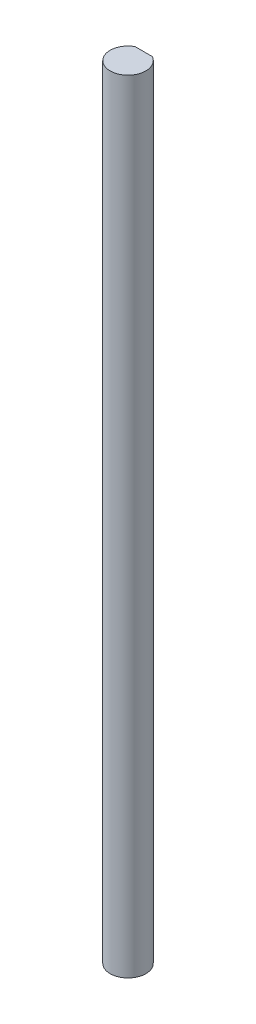
SolidWorks part; units mm, degrees
material "AISI 1045 Steel, cold drawn"
ref_plane "Front Plane" through (0, 0, 0) normal (0, 0, 1) x (1, 0, 0)
ref_plane "Top Plane" through (0, 0, 0) normal (0, 1, 0) x (1, 0, 0)
ref_plane "Right Plane" through (0, 0, 0) normal (1, 0, 0) x (0, 0, -1)
sketch "Sketch1" plane through (0, 0, 0) normal (0, 1, 0) x (1, 0, 0)
  line L0 (-1.9365, 3.5) -> (1.9365, 3.5)
  arc A0 (-1.9365, 3.5) -> (1.9365, 3.5) centre (0, 0) ccw
  dimension "D1" = 8
  dimension "D2" = 3.5
extrude "Boss-Extrude1" add sketch "Sketch1" along normal blind 175
hole_wizard "Tap Drill for M3x0.5 Tap1" positions "Sketch2" profile "Sketch3" hole size "M3x0.5" standard "ANSI Metric"
sketch "Sketch2" plane through (0, 0, -3.5) normal (0, 0, -1) x (-1, 0, 0)
  line L0 (-1.9365, 175) -> (1.9365, 175) construction
  point P0 (0, 171.5)
  point P5 (0, 175)
  dimension "D1" = 3.5
sketch "Sketch3" plane through (0, 171.5, -3.5) normal (1, 0, 0) x (0, 1, 0)
  line L0 (0, 0) -> (0, 5.7511)
  line L1 (0, 5.7511) -> (1.25, 5)
  line L2 (1.25, 5) -> (1.25, 0.025)
  line L3 (1.25, 0.025) -> (1.275, 0)
  line L5 (1.275, 0) -> (0, 0)
  line L6 (-1.25, 0.025) -> (-1.275, 0) construction
  line L10 (0, 5.7511) -> (-1.25, 5) construction
  line L11 (0, -6.35) -> (0, 107.95) construction
  dimension "Hole Dia." = 2.5
  dimension "Hole Depth" = 5
  dimension "Near C'Sink Dia." = 2.55
  dimension "Near C'Sink Angle" = 90
  dimension "Drill Angle" = 118
